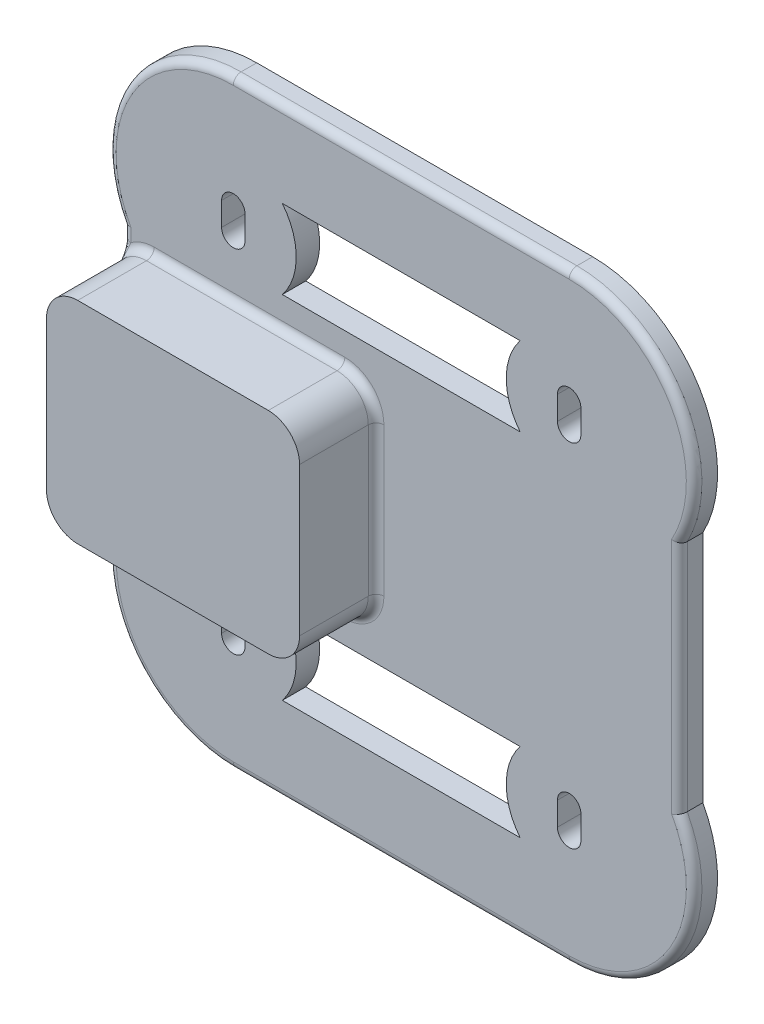
SolidWorks part; units mm, degrees
ref_plane "Front Plane" through (0, 0, 0) normal (0, 0, 1) x (1, 0, 0)
ref_plane "Top Plane" through (0, 0, 0) normal (0, 1, 0) x (1, 0, 0)
ref_plane "Right Plane" through (0, 0, 0) normal (1, 0, 0) x (0, 0, -1)
sketch "Sketch1" plane through (0, 0, 0) normal (0, 0, 1) x (1, 0, 0)
  line L0 (21.5, 16) -> (-21.5, 16) construction
  line L1 (21.5, 16) -> (-21.5, 16)
  line L2 (0, 0) -> (0, -22.5) construction
  line L3 (0, -22.5) -> (-43.4531, -22.5) construction
  line L4 (-35.6203, -7.5245) -> (-35.6203, -37.4755)
  line L5 (35.6203, -7.5245) -> (35.6203, -37.4755)
  line L6 (21.5, -61) -> (-21.5, -61)
  line L7 (200000, -13) -> (-200003.1303, -13) construction
  line L8 (200000, -13) -> (-200003.1303, -13) construction
  line L9 (200000, -32) -> (-200003.1303, -32) construction
  line L10 (-21.5, -1.5) -> (-21.5, 1.5) construction
  line L11 (-23, -1.5) -> (-23, 1.5)
  line L12 (-20, -1.5) -> (-20, 1.5)
  line L13 (21.5, -1.5) -> (21.5, 1.5) construction
  line L14 (20, -1.5) -> (20, 1.5)
  line L15 (23, -1.5) -> (23, 1.5)
  line L16 (21.5, -46.5) -> (21.5, -43.5) construction
  line L17 (20, -46.5) -> (20, -43.5)
  line L18 (23, -46.5) -> (23, -43.5)
  line L19 (-21.5, -46.5) -> (-21.5, -43.5) construction
  line L20 (-23, -46.5) -> (-23, -43.5)
  line L21 (-20, -46.5) -> (-20, -43.5)
  line L24 (15.229, 5.0542) -> (-15.229, 5.0542) construction
  line L25 (-15.229, -5.0542) -> (15.229, -5.0542) construction
  line L26 (15.229, 5.0542) -> (-15.229, 5.0542)
  line L27 (-15.229, -5.0542) -> (15.229, -5.0542)
  line L28 (-15.229, -39.9458) -> (15.229, -39.9458)
  line L29 (15.229, -50.0542) -> (-15.229, -50.0542)
  arc A0 (-21.5, 16) -> (-35.6203, -7.5245) centre (-21.5, 0) ccw construction
  arc A1 (35.6203, -7.5245) -> (21.5, 16) centre (21.5, 0) ccw construction
  arc A2 (-21.5, 16) -> (-35.6203, -7.5245) centre (-21.5, 0) ccw
  arc A3 (35.6203, -7.5245) -> (21.5, 16) centre (21.5, 0) ccw
  circle A4 centre (-21.5, 0) radius 1.5 construction
  circle A5 centre (21.5, 0) radius 1.5 construction
  circle A6 centre (-21.5, 0) radius 1.5 construction
  circle A7 centre (21.5, 0) radius 1.5 construction
  circle A8 centre (21.5, -45) radius 1.5 construction
  circle A9 centre (-21.5, -45) radius 1.5 construction
  arc A10 (35.6203, -37.4755) -> (21.5, -61) centre (21.5, -45) cw
  arc A11 (-21.5, -61) -> (-35.6203, -37.4755) centre (-21.5, -45) cw
  arc A12 (-23, -1.5) -> (-20, -1.5) centre (-21.5, -1.5) ccw
  arc A13 (-20, 1.5) -> (-23, 1.5) centre (-21.5, 1.5) ccw
  arc A14 (20, -1.5) -> (23, -1.5) centre (21.5, -1.5) ccw
  arc A15 (23, 1.5) -> (20, 1.5) centre (21.5, 1.5) ccw
  arc A16 (20, -46.5) -> (23, -46.5) centre (21.5, -46.5) ccw
  arc A17 (23, -43.5) -> (20, -43.5) centre (21.5, -43.5) ccw
  arc A18 (-23, -46.5) -> (-20, -46.5) centre (-21.5, -46.5) ccw
  arc A19 (-20, -43.5) -> (-23, -43.5) centre (-21.5, -43.5) ccw
  arc A20 (-15.229, -5.0542) -> (-15.229, 5.0542) centre (-21.5, 0) ccw construction
  arc A21 (15.229, 5.0542) -> (15.229, -5.0542) centre (21.5, 0) ccw construction
  arc A22 (-15.229, -5.0542) -> (-15.229, 5.0542) centre (-21.5, 0) ccw
  arc A23 (15.229, 5.0542) -> (15.229, -5.0542) centre (21.5, 0) ccw
  arc A24 (15.229, -50.0542) -> (15.229, -39.9458) centre (21.5, -45) cw
  arc A25 (-15.229, -39.9458) -> (-15.229, -50.0542) centre (-21.5, -45) cw
  point P21 (-35.6203, -22.5)
  point P22 (35.6203, -22.5)
  point P30 (-21.5, 0)
  point P37 (21.5, 0)
  point P44 (21.5, -45)
  point P51 (-21.5, -45)
  dimension "D1" = 19
  dimension "D2" = 3
  dimension "D3" = 3
extrude "Boss-Body" add sketch "Sketch1" along normal blind 3
sketch "Sketch2" [suppressed] plane through (0, 0, 0) normal (0, 0, -1) x (-1, 0, 0)
  line L0 (-35.6203, -22.5) -> (35.6203, -22.5) construction
  line L1 (-35.6203, -37.4755) -> (-35.6203, -7.5245) construction
  line L2 (35.6203, -7.5245) -> (35.6203, -37.4755) construction
  line L4 (35.6203, -19.7) -> (-35.6203, -19.7)
  line L5 (35.6203, -19.7) -> (35.6203, -25.3)
  line L6 (35.6203, -25.3) -> (-35.6203, -25.3)
  line L7 (-35.6203, -19.7) -> (-35.6203, -25.3)
  line L8 (35.6203, -19.7) -> (-35.6203, -25.3) construction
  line L9 (35.6203, -25.3) -> (-35.6203, -19.7) construction
  point P6 (0, -22.5)
  dimension "D1" = 5.6
extrude "Boss-Stabilizer" [suppressed] add sketch "Sketch2" along normal blind 3
fillet "Fillet-Outside features" [suppressed] radius 1
sketch "Sketch3" plane through (0, 0, 3) normal (0, 0, 1) x (1, 0, 0)
  line L0 (-35.6203, -22.5) -> (35.6203, -22.5) construction
  line L1 (-35.6203, -7.5245) -> (-35.6203, -37.4755) construction
  line L2 (35.6203, -37.4755) -> (35.6203, -7.5245) construction
ref_plane "PlaneCenter" through (0, -22.5, 0) normal (0, -1, 0) x (-1, 0, 0)
sketch "Sketch11" [suppressed] plane through (0, 0, 3) normal (0, 0, 1) x (1, 0, 0)
  line L0 (-36.1203, -23) -> (36.1203, -23) construction
  line L1 (-36.1203, -7.5245) -> (-36.1203, -38.4755) construction
  line L2 (36.1203, -38.4755) -> (36.1203, -7.5245) construction
  line L3 (-36.1203, -7.5245) -> (36.1203, -7.5245) construction
  line L4 (-36.1203, -38.4755) -> (36.1203, -38.4755) construction
  line L5 (0, -7.5245) -> (0, -38.4755) construction
  line L6 (-33.1203, -7.5245) -> (-33.1203, -38.4755) construction
  line L7 (33.1203, -7.5245) -> (33.1203, -38.4755) construction
  line L8 (-33.1203, -22) -> (33.1203, -22)
  line L9 (-33.1203, -19) -> (33.1203, -19)
  line L10 (-33.1203, -14) -> (33.1203, -14)
  line L11 (-33.1203, -17) -> (33.1203, -17)
  line L12 (-33.1203, -9) -> (33.1203, -9)
  line L13 (-33.1203, -12) -> (33.1203, -12)
  line L14 (-33.1203, -24) -> (33.1203, -24)
  line L15 (-33.1203, -27) -> (33.1203, -27)
  line L16 (-33.1203, -29) -> (33.1203, -29)
  line L17 (-33.1203, -32) -> (33.1203, -32)
  line L18 (-33.1203, -34) -> (33.1203, -34)
  line L19 (-33.1203, -37) -> (33.1203, -37)
  line L20 (-33.1203, -17) -> (-36.1203, -17)
  line L21 (-36.1203, -17) -> (-36.1203, -19)
  line L22 (-36.1203, -19) -> (-33.1203, -19)
  line L23 (33.1203, -17) -> (33.1203, -19)
  line L24 (33.1203, -24) -> (36.1203, -24)
  line L25 (36.1203, -24) -> (36.1203, -22)
  line L26 (36.1203, -22) -> (33.1203, -22)
  line L27 (-33.1203, -22) -> (-33.1203, -24)
  line L28 (-36.1203, -7.5245) -> (-36.1203, -38.4755) construction
  line L29 (36.1203, -7.5245) -> (36.1203, -38.4755) construction
  line L30 (-33.1203, -27) -> (-36.1203, -27)
  line L31 (-36.1203, -27) -> (-36.1203, -29)
  line L32 (-36.1203, -29) -> (-33.1203, -29)
  line L33 (33.1203, -32) -> (36.1203, -32)
  line L34 (36.1203, -32) -> (36.1203, -34)
  line L35 (36.1203, -34) -> (33.1203, -34)
  line L36 (33.1203, -14) -> (36.1203, -14)
  line L37 (36.1203, -14) -> (36.1203, -12)
  line L38 (36.1203, -12) -> (33.1203, -12)
  line L39 (-33.1203, -9) -> (-36.1203, -9)
  line L40 (-36.1203, -9) -> (-36.1203, -7.5245)
  line L41 (-36.1203, -7.5245) -> (33.1203, -7.5245)
  line L42 (33.1203, -7.5245) -> (33.1203, -9)
  line L43 (-33.1203, -32) -> (-33.1203, -34)
  line L44 (33.1203, -37) -> (33.1203, -38.4755)
  line L45 (33.1203, -38.4755) -> (-36.1203, -38.4755)
  line L46 (-36.1203, -38.4755) -> (-36.1203, -37)
  line L47 (-36.1203, -37) -> (-33.1203, -37)
  line L48 (33.1203, -27) -> (33.1203, -29)
  line L49 (-33.1203, -12) -> (-33.1203, -14)
  dimension "D1" = 3
  dimension "D2" = 2
  dimension "D3" = 3
  dimension "D4" = 3
  dimension "D5" = 4
extrude "Cut-Extrude4" [suppressed] cut sketch "Sketch11" against normal through all
fillet "Fillet1" [suppressed] radius 3
fillet "Fillet2" [suppressed] radius 1
sketch "Sketch12" [suppressed] plane through (0, 0, 3) normal (0, 0, 1) x (1, 0, 0)
  line L0 (0, 16) -> (0, -62) construction
  line L1 (22, 16) -> (-22, 16) construction
  line L2 (-22, -62) -> (22, -62) construction
  line L3 (0, -23) -> (42.3033, -23) construction
  line L4 (-4, 5.0542) -> (-4, 11.0542)
  line L5 (15.729, 5.0542) -> (-15.729, 5.0542) construction
  line L6 (-4, 5.0542) -> (4, 5.0542)
  line L7 (4, 5.0542) -> (4, 11.0542)
  line L8 (-4, -51.0542) -> (4, -51.0542)
  line L9 (-4, -51.0542) -> (-4, -57.0542)
  line L10 (4, -51.0542) -> (4, -57.0542)
  arc A0 (-4, 11.0542) -> (4, 11.0542) centre (0, 11.0542) cw
  arc A1 (-4, -57.0542) -> (4, -57.0542) centre (0, -57.0542) ccw
  point P16 (0, 5.0542)
  dimension "D3" = 4
  dimension "D1" = 8
  dimension "D2" = 6
extrude "Boss-Extrude4" [suppressed] add sketch "Sketch12" along normal blind 8
sketch "Sketch13" [suppressed] plane through (4, 0, 0) normal (1, 0, 0) x (0, 0, -1)
  line L0 (-11, -61.0542) -> (-11, -55.0542)
  line L1 (-11, -61.0542) -> (-5, -61.0542)
  line L2 (-11, -57.0542) -> (-11, -51.0542) construction
  line L3 (-11, -57.0542) -> (-11, -61.0542) construction
  line L4 (-11, -61.0542) -> (-3, -61.0542) construction
  line L5 (-11, -51.0542) -> (-3, -51.0542) construction
  line L6 (-3, -38.4755) -> (-3, -62) construction
  line L7 (-7, -51.0542) -> (-7, 5.0542) construction
  line L8 (-11, 5.0542) -> (-3, 5.0542) construction
  line L9 (-7, -23) -> (-15.8814, -23) construction
  line L10 (-11, 15.0542) -> (-5, 15.0542)
  line L11 (-11, 15.0542) -> (-11, 9.0542)
  arc A0 (-11, -55.0542) -> (-5, -61.0542) centre (-11, -61.0542) cw
  arc A1 (-11, 9.0542) -> (-5, 15.0542) centre (-11, 15.0542) ccw
  dimension "D1" = 2
  dimension "D2" = 4
extrude "Cut-Extrude6" [suppressed] cut sketch "Sketch13" against normal up to next
sketch "Sketch14" [suppressed] plane through (0, -51.0542, 0) normal (0, 1, 0) x (1, 0, 0)
  line L0 (-4, -7) -> (4, -7) construction
  line L1 (-4, -11) -> (-4, -3) construction
  line L2 (4, -11) -> (4, -3) construction
  circle A0 centre (0, -7) radius 1.5
  dimension "D1" = 3
extrude "Cut-Extrude7" [suppressed] cut sketch "Sketch14" against normal through all both and the other way through all
sketch "Sketch17" [suppressed] plane through (0, -62, 0) normal (0, -1, 0) x (1, 0, 0)
  circle A0 centre (0, 7) radius 2.875
  dimension "D1" = 5.75
extrude "Cut-Extrude9" [suppressed] cut sketch "Sketch17" against normal offset from surface (8.9458 mm away) 2 up to face at (0, -50.0542, 1.5)
sketch "Sketch18" [suppressed] plane through (0, 16, 0) normal (0, 1, 0) x (1, 0, 0)
  line L0 (0, -7) -> (2.75, -7) construction
  line L1 (0, -3.8246) -> (-2.75, -5.4123)
  line L2 (-2.75, -5.4123) -> (-2.75, -8.5877)
  line L3 (-2.75, -8.5877) -> (0, -10.1754)
  line L4 (0, -10.1754) -> (2.75, -8.5877)
  line L5 (2.75, -8.5877) -> (2.75, -5.4123)
  line L6 (2.75, -5.4123) -> (0, -3.8246)
  circle A0 centre (0, -7) radius 2.75 construction
  dimension "D1" = 5.5
extrude "Cut-Extrude10" [suppressed] cut sketch "Sketch18" against normal offset from surface (8.9458 mm away) 2 up to face at (0, 5.0542, 1.5)
fillet "Fillet-3mm-t" [suppressed] radius 3
fillet "Fillet4" [suppressed] radius 1
fillet "Fillet7" [suppressed] radius 0.5
sketch "Sketch19" plane through (0, 0, 3) normal (0, 0, 1) x (1, 0, 0)
  line L0 (-35.6203, -22.5) -> (35.6203, -22.5) construction
  line L1 (-35.6203, -7.5245) -> (-35.6203, -37.4755) construction
  line L2 (35.6203, -37.4755) -> (35.6203, -7.5245) construction
  line L4 (-3.2203, -36) -> (-35.6203, -36)
  line L5 (-3.2203, -36) -> (-3.2203, -9)
  line L6 (-3.2203, -9) -> (-35.6203, -9)
  line L7 (-35.6203, -36) -> (-35.6203, -9)
  line L8 (-3.2203, -36) -> (-35.6203, -9) construction
  line L9 (-3.2203, -9) -> (-35.6203, -36) construction
  point P6 (-19.4203, -22.5)
  dimension "D1" = 27
  dimension "D2" = 32.4
extrude "Boss-Extrude5" add sketch "Sketch19" along normal blind 9.8
sketch "Sketch20" plane through (0, 0, 12.8) normal (0, 0, 1) x (1, 0, 0)
  line L0 (-35.6203, -22.5) -> (-3.2203, -22.5) construction
  line L1 (-35.6203, -9) -> (-35.6203, -36) construction
  line L2 (-3.2203, -36) -> (-3.2203, -9) construction
  line L3 (-19.4203, -9) -> (-19.4203, -36) construction
  line L4 (-3.2203, -9) -> (-35.6203, -9) construction
  line L5 (-35.6203, -36) -> (-3.2203, -36) construction
  circle A0 centre (-29.4203, -12.5) radius 1.6
  circle A1 centre (-9.4203, -12.5) radius 1.6
  circle A2 centre (-9.4203, -32.5) radius 1.6
  circle A3 centre (-29.4203, -32.5) radius 1.6
  dimension "D1" = 20
  dimension "D2" = 20
  dimension "D3" = 3.2
ref_plane "Plane1" through (0, 0, 9.8) normal (0, 0, 1) x (1, 0, 0)
extrude "Cut-Extrude11" [suppressed] cut sketch "Sketch20" against normal up to surface (10 mm away) up to face at (0, -45, 3)
sketch "Sketch21" [suppressed] plane through (0, 0, 10) normal (0, 0, 1) x (1, 0, 0)
  line L0 (-35.6203, -22.5) -> (-3.2203, -22.5) construction
  line L1 (-29.4203, -12.5) -> (-29.4203, -9) construction
  line L2 (-26.6203, -9) -> (-32.2203, -9)
  line L3 (-32.2203, -9) -> (-32.2203, -15.5)
  line L4 (-32.2203, -15.5) -> (-26.6203, -15.5)
  line L5 (-26.6203, -9) -> (-26.6203, -15.5)
  line L6 (-12.2203, -9) -> (-12.2203, -15.5)
  line L7 (-35.6203, -9) -> (-35.6203, -36) construction
  line L8 (-3.2203, -36) -> (-3.2203, -9) construction
  line L9 (-19.4203, -9) -> (-19.4203, -36) construction
  line L10 (-3.2203, -9) -> (-35.6203, -9) construction
  line L11 (-35.6203, -36) -> (-3.2203, -36) construction
  line L12 (-6.6203, -15.5) -> (-12.2203, -15.5)
  line L13 (-12.2203, -9) -> (-6.6203, -9)
  line L14 (-6.6203, -9) -> (-6.6203, -15.5)
  line L15 (-26.6203, -36) -> (-32.2203, -36)
  line L16 (-32.2203, -36) -> (-32.2203, -29.5)
  line L17 (-32.2203, -29.5) -> (-26.6203, -29.5)
  line L18 (-26.6203, -36) -> (-26.6203, -29.5)
  line L19 (-6.6203, -36) -> (-6.6203, -29.5)
  line L20 (-12.2203, -36) -> (-6.6203, -36)
  line L21 (-12.2203, -36) -> (-12.2203, -29.5)
  line L22 (-6.6203, -29.5) -> (-12.2203, -29.5)
  point P7 (-29.4203, -15.5)
  dimension "D1" = 5.6
  dimension "D2" = 3
extrude "Cut-Extrude12" [suppressed] cut sketch "Sketch21" against normal blind 4
sketch "Sketch22" [suppressed] plane through (0, 0, 10) normal (0, 0, -1) x (-1, 0, 0)
  circle A0 centre (29.4203, -32.5) radius 1.6 construction
  circle A1 centre (29.4203, -12.5) radius 1.6 construction
  circle A2 centre (9.4203, -12.5) radius 1.6 construction
  circle A3 centre (9.4203, -32.5) radius 1.6 construction
  circle A4 centre (29.4203, -32.5) radius 1.6
  circle A5 centre (29.4203, -12.5) radius 1.6
  circle A6 centre (9.4203, -12.5) radius 1.6
  circle A7 centre (9.4203, -32.5) radius 1.6
extrude "Boss-Extrude7" [suppressed] add sketch "Sketch22" against normal blind 0.6
sketch "Sketch23" plane through (0, 0, 12.8) normal (0, 0, 1) x (1, 0, 0)
  line L0 (-19.4203, -9) -> (-19.4203, -36) construction
  line L1 (-3.2203, -9) -> (-35.6203, -9) construction
  line L2 (-35.6203, -36) -> (-3.2203, -36) construction
  line L3 (-15.4203, -9) -> (-23.4203, -9)
  line L4 (-23.4203, -9) -> (-23.4203, -36)
  line L5 (-23.4203, -36) -> (-15.4203, -36)
  line L6 (-15.4203, -9) -> (-15.4203, -36)
  dimension "D1" = 8
extrude "Cut-Extrude13" [suppressed] cut sketch "Sketch23" against normal up to surface (10 mm away) up to face at (0, -45, 3)
fillet "Fillet8" radius 4 4 edges at (-3.2203, -9, 7.9) (-3.2203, -36, 7.9) (-35.6203, -36, 7.9) (-35.6203, -9, 7.9)
fillet "Fillet9" radius 1 16 edges at (-19.4203, -9, 3) (-4.3919, -10.1716, 3) (-3.2203, -22.5, 3) (-4.3919, -34.8284, 3) (-34.4487, -34.8284, 3) (-19.4203, -36, 3) (-34.4487, -10.1716, 3) (35.2184, 8.2343, 3) (0, 16, 3) (35.2184, -53.2343, 3) (0, -61, 3) (35.6203, -22.5, 3) (-35.2184, 8.2343, 3) (-35.6203, -10.2622, 3) (-35.6203, -34.7378, 3) (-35.2184, -53.2343, 3)
